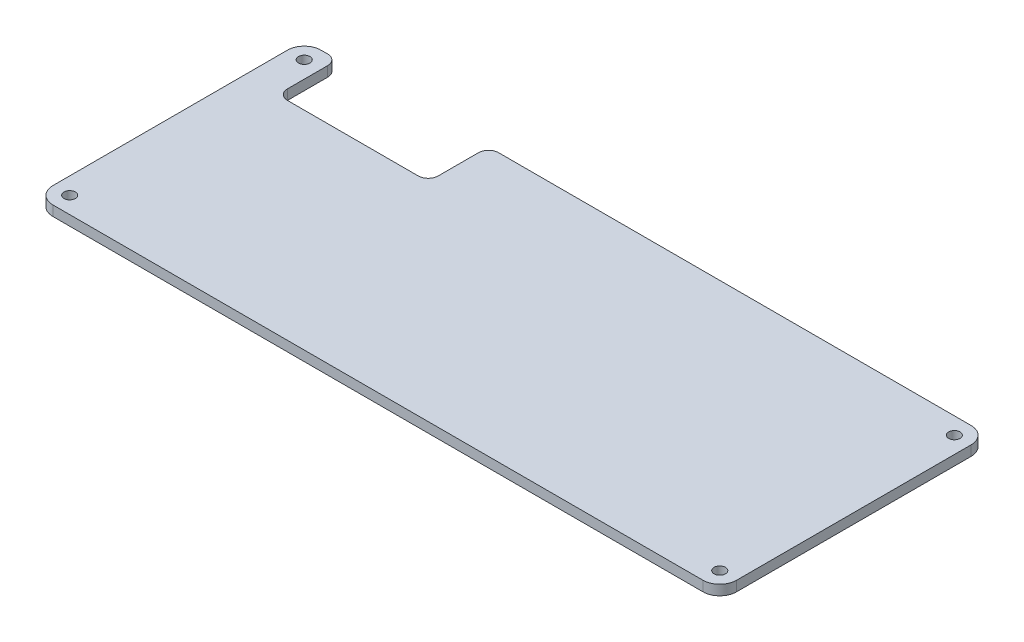
SolidWorks part; units mm, degrees
ref_plane "Front" through (0, 0, 0) normal (0, 0, 1) x (1, 0, 0)
ref_plane "Top" through (0, 0, 0) normal (0, 1, 0) x (1, 0, 0)
ref_plane "Right" through (0, 0, 0) normal (1, 0, 0) x (0, 0, -1)
sketch "Esquisse1" plane through (0, 0, 0) normal (0, 1, 0) x (1, 0, 0)
  line L1 (0, 0) -> (204, 0)
  line L2 (0, 0) -> (0, 80)
  line L3 (0, 80) -> (204, 80)
  line L4 (204, 0) -> (204, 80)
  dimension "D1" = 204
  dimension "D2" = 80
extrude "Boss.-Extru.1" add sketch "Esquisse1" along normal blind 3
fillet "Congé1" radius 5 4 edges at (0, 1.5, -80) (0, 1.5, 0) (204, 1.5, -80) (204, 1.5, 0)
sketch "Esquisse2" plane through (0, 3, 0) normal (0, 1, 0) x (1, 0, 0)
  line L0 (0, 75) -> (0, 5) construction
  line L1 (199, 80) -> (5, 80) construction
  line L2 (5, 0) -> (199, 0) construction
  line L3 (204, 5) -> (204, 75) construction
  line L5 (10, 80) -> (55, 80)
  line L6 (10, 80) -> (10, 62)
  line L7 (10, 62) -> (55, 62)
  line L8 (55, 80) -> (55, 62)
  circle A0 centre (5, 75) radius 1
  circle A1 centre (199, 75) radius 1
  circle A2 centre (199, 5) radius 1
  circle A3 centre (5, 5) radius 1
  dimension "D9" = 2
  dimension "D10" = 2
  dimension "D11" = 2
  dimension "D12" = 2
  dimension "D1" = 5
  dimension "D2" = 5
  dimension "D3" = 5
  dimension "D4" = 5
  dimension "D5" = 5
  dimension "D6" = 5
  dimension "D7" = 5
  dimension "D8" = 5
  dimension "D13" = 10
  dimension "D14" = 45
  dimension "D15" = 18
extrude "Enlèv. mat.-Extru.1" cut sketch "Esquisse2" against normal through all
hole_wizard "Dégagement M31" positions "Esquisse3" profile "Esquisse4" hole size "M3" standard "ISO"
sketch "Esquisse3" plane through (0, 3, 0) normal (0, 1, 0) x (1, 0, 0)
  point P0 (199, 5)
  point P3 (5, 5)
  point P6 (5, 75)
  point P9 (199, 75)
sketch "Esquisse4" plane through (199, 3, -5) normal (1, 0, 0) x (0, 0, 1)
  line L0 (0, 0) -> (0, 11.0215)
  line L1 (0, 11.0215) -> (1.7, 10)
  line L2 (1.7, 10) -> (1.7, 0)
  line L5 (1.7, 0) -> (0, 0)
  line L10 (0, 11.0215) -> (-1.7, 10) construction
  line L11 (0, -6.35) -> (0, 107.95) construction
  dimension "Diamètre du perçage" = 3.4
  dimension "Profondeur du perçage" = 10
  dimension "Angle de pointe" = 118
fillet "Congé2" radius 3 4 edges at (55, 1.5, -62) (55, 1.5, -80) (10, 1.5, -80) (10, 1.5, -62)
